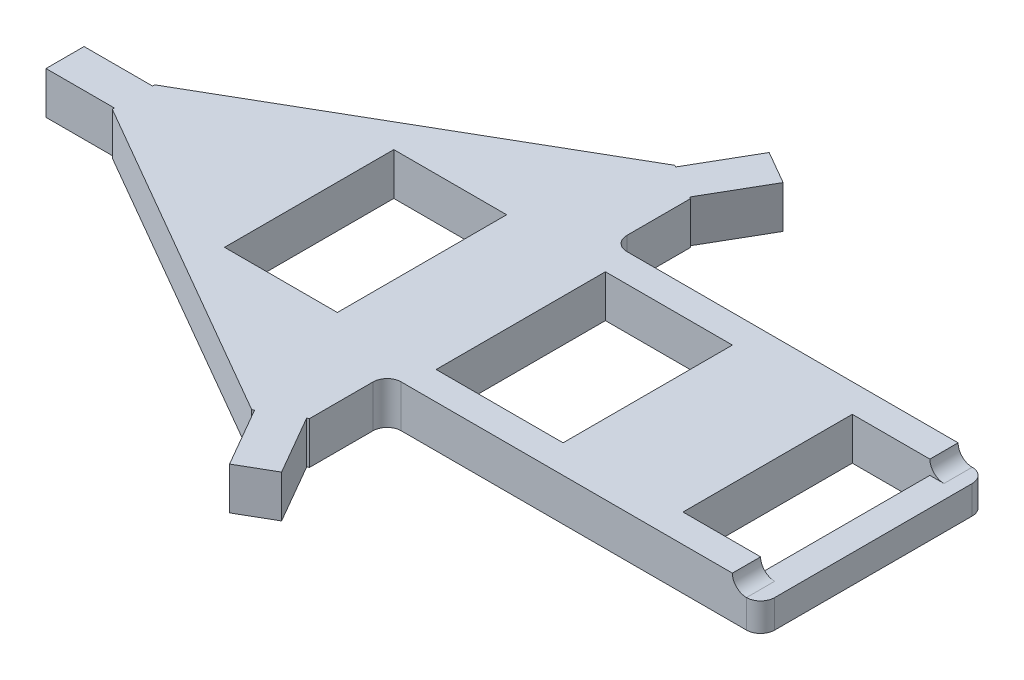
SolidWorks part; units mm, degrees
ref_plane "Front Plane" through (0, 0, 0) normal (0, 0, 1) x (1, 0, 0)
ref_plane "Top Plane" through (0, 0, 0) normal (0, 1, 0) x (1, 0, 0)
ref_plane "Right Plane" through (0, 0, 0) normal (1, 0, 0) x (0, 0, -1)
sketch "Sketch1" plane through (0, 0, 0) normal (0, 1, 0) x (1, 0, 0)
  line L0 (0, 0) -> (101.6, 0)
  line L1 (0, 0) -> (-50.8, 87.9882)
  line L2 (0, 0) -> (-50.8, -87.9882)
  line L3 (20, -12.3081) -> (83, -12.3081)
  line L4 (20, -12.3081) -> (20, 12.3081)
  line L5 (83, -12.3081) -> (83, 12.3081)
  line L6 (20, 12.3081) -> (83, 12.3081)
  line L7 (20, -12.3081) -> (83, 12.3081) construction
  line L8 (83, -12.3081) -> (20, 12.3081) construction
  line L9 (83, 0) -> (83, -58.5966) construction
  line L10 (20, 12.3081) -> (0, 12.3081)
  line L11 (20, 12.3081) -> (20, -12.3081)
  line L12 (20, -12.3081) -> (0, -12.3081)
  line L13 (0, 12.3081) -> (0, -12.3081)
  line L14 (51.5, 12.3081) -> (51.5, -12.3081) construction
  line L15 (83, -58.5966) -> (119.7868, -58.5966)
  line L16 (83, -58.5966) -> (83, 61.6733)
  line L17 (83, 61.6733) -> (119.7868, 61.6733)
  line L18 (119.7868, -58.5966) -> (119.7868, 61.6733)
  line L19 (83, -8.5) -> (20, -8.5)
  line L20 (83, -8.5) -> (83, 8.5)
  line L21 (83, 8.5) -> (20, 8.5)
  line L22 (20, -8.5) -> (20, 8.5)
  line L23 (83, -8.5) -> (20, 8.5) construction
  line L24 (83, 8.5) -> (20, -8.5) construction
  line L25 (20, 8.5) -> (40, 8.5)
  line L26 (20, 8.5) -> (20, 12.3081)
  line L27 (20, 12.3081) -> (40, 12.3081)
  line L28 (40, 8.5) -> (40, 12.3081)
  line L29 (63, 8.5) -> (63, 12.3081)
  line L30 (63, -8.5) -> (63, -12.3081)
  line L31 (40, -8.5) -> (40, -12.3081)
  circle A0 centre (0, 0) radius 101.6
  circle A1 centre (0, 0) radius 20
  point P7 (51.5, 0)
  point P19 (51.5, 0)
  dimension "D1" = 120
  dimension "D8" = 203.2
  dimension "D2" = 120
  dimension "D3" = 63
  dimension "D4" = 20
  dimension "D5" = 0
  dimension "D6" = 17
  dimension "D7" = 20
sketch "Sketch2" plane through (0, 0, 0) normal (0, 1, 0) x (1, 0, 0)
  circle A0 centre (0, 0) radius 88.9
  dimension "D1" = 177.8
extrude "Boss-Extrude1" add sketch "Sketch2" along normal blind 3.175
sketch "Sketch4" plane through (0, 3.175, 0) normal (0, 1, 0) x (1, 0, 0)
  line L0 (-88.9, 0) -> (88.9, 0) construction
  line L1 (52.07, 0) -> (52.07, 13.9847) construction
  line L2 (16.51, 15.5) -> (38.51, 15.5)
  line L3 (16.51, 15.5) -> (16.51, -15.5)
  line L4 (16.51, -15.5) -> (38.51, -15.5)
  line L5 (38.51, 15.5) -> (38.51, -15.5)
  line L6 (16.51, 15.5) -> (38.51, -15.5) construction
  line L7 (16.51, -15.5) -> (38.51, 15.5) construction
  line L8 (-16.51, -16.51) -> (16.51, -16.51)
  line L9 (-16.51, -16.51) -> (-16.51, 16.51)
  line L10 (-16.51, 16.51) -> (16.51, 16.51)
  line L11 (16.51, -16.51) -> (16.51, 16.51)
  line L12 (-16.51, -16.51) -> (16.51, 16.51) construction
  line L13 (-16.51, 16.51) -> (16.51, -16.51) construction
  line L14 (16.51, 15.5) -> (23.51, 15.5)
  line L15 (16.51, 15.5) -> (16.51, -15.5)
  line L16 (16.51, -15.5) -> (23.51, -15.5)
  line L17 (23.51, 15.5) -> (23.51, -15.5)
  line L18 (23.51, 8.5) -> (38.51, 8.5)
  line L19 (23.51, 8.5) -> (23.51, -8.5)
  line L20 (23.51, -8.5) -> (38.51, -8.5)
  line L21 (38.51, 8.5) -> (38.51, -8.5)
  line L22 (80.63, -8.5) -> (65.63, -8.5)
  line L23 (65.63, 8.5) -> (65.63, -8.5)
  line L24 (80.63, 8.5) -> (65.63, 8.5)
  line L25 (80.63, 8.5) -> (80.63, -8.5)
  line L26 (87.63, -15.5) -> (65.63, -15.5)
  line L27 (65.63, 15.5) -> (65.63, -15.5)
  line L28 (87.63, 15.5) -> (65.63, 15.5)
  line L29 (87.63, 15.5) -> (87.63, -15.5)
  line L30 (87.63, -15.5) -> (80.63, -15.5)
  line L31 (80.63, 15.5) -> (80.63, -15.5)
  line L32 (87.63, 15.5) -> (80.63, 15.5)
  line L33 (87.63, 15.5) -> (87.63, -15.5)
  line L34 (80.63, -31.75) -> (80.63, 31.75)
  line L35 (80.63, -31.75) -> (102.0422, -31.75)
  line L36 (80.63, 31.75) -> (102.0422, 31.75)
  line L37 (102.0422, -31.75) -> (102.0422, 31.75)
  circle A1 centre (0, 0) radius 88.9
  circle A2 centre (0, 0) radius 88.9
  point P5 (27.51, 0)
  dimension "D2" = 22
  dimension "D3" = 33.02
  dimension "D4" = 33.02
  dimension "D5" = 31
  dimension "D6" = 0
  dimension "D7" = 7
  dimension "D8" = 17
  dimension "D9" = 8.5
  dimension "D10" = 35.56
  dimension "D11" = 63.5
  dimension "D12" = 31.75
  dimension "D1" = 0
extrude "Cut-Extrude2" cut sketch "Sketch4" against normal through all contours L17 L2 L3 L4 | L25 L24 L23 L22 | L17 L20 L5 L18 | L34 L35 L37 L36 region at (20.01, 3.175, 0) region at (31.01, 3.175, 0) region at (73.13, 3.175, 0)
pattern_circular "CirPattern1" count 3 over 360 about axis through (0, 3.175, 0) along (0, 1, 0) of "Cut-Extrude2"
sketch "Sketch5" plane through (0, 3.175, 0) normal (0, 1, 0) x (1, 0, 0)
  line L1 (-16.51, -15.5) -> (16.51, -15.5)
  line L2 (-16.51, -15.5) -> (-16.51, 15.5)
  line L3 (-16.51, 15.5) -> (16.51, 15.5)
  line L4 (16.51, -15.5) -> (16.51, 15.5)
  line L5 (-16.51, -15.5) -> (16.51, 15.5) construction
  line L6 (-16.51, 15.5) -> (16.51, -15.5) construction
  line L7 (-5.49, -15.5) -> (16.51, -15.5)
  line L8 (-5.49, -15.5) -> (-5.49, 15.5)
  line L9 (-5.49, 15.5) -> (16.51, 15.5)
  line L10 (16.51, -15.5) -> (16.51, 15.5)
  line L11 (-5.49, -15.5) -> (16.51, 15.5) construction
  line L12 (-5.49, 15.5) -> (16.51, -15.5) construction
  point P0 (0, 0)
  point P7 (5.51, 0)
  dimension "D1" = 22
sketch "Sketch6" plane through (0, 3.175, 0) normal (0, 1, 0) x (1, 0, 0)
  line L0 (5.1684, 22.0481) -> (16.51, 15.5)
  line L1 (16.51, 15.5) -> (16.51, -15.5)
  line L2 (16.51, -15.5) -> (5.1684, -22.0481)
  line L3 (5.1684, -22.0481) -> (-21.6784, -6.5481)
  line L4 (-21.6784, -6.5481) -> (-21.6784, 6.5481)
  line L5 (-21.6784, 6.5481) -> (5.1684, 22.0481)
  line L21 (-32.9538, -74.0776) -> (-12.8187, -85.7026)
  line L24 (80.63, -31.75) -> (80.63, -8.5)
  line L25 (80.63, -8.5) -> (65.63, -8.5)
  line L26 (65.63, -8.5) -> (65.63, 8.5)
  line L27 (65.63, 8.5) -> (80.63, 8.5)
  line L28 (80.63, 8.5) -> (80.63, 31.75)
  line L31 (-12.8187, 85.7026) -> (-32.9538, 74.0776)
  line L32 (-32.9538, 74.0776) -> (-25.4538, 61.0872)
  line L33 (-25.4538, 61.0872) -> (-40.1762, 52.5872)
  line L34 (-40.1762, 52.5872) -> (-47.6762, 65.5776)
  line L35 (-47.6762, 65.5776) -> (-67.8113, 53.9526)
  line L38 (-67.8113, -53.9526) -> (-47.6762, -65.5776)
  line L39 (-47.6762, -65.5776) -> (-40.1762, -52.5872)
  line L40 (-40.1762, -52.5872) -> (-25.4538, -61.0872)
  line L41 (-25.4538, -61.0872) -> (-32.9538, -74.0776)
  line L42 (-32.9538, -74.0776) -> (-12.8187, -85.7026)
  line L45 (80.63, -31.75) -> (80.63, -8.5)
  line L46 (80.63, -8.5) -> (65.63, -8.5)
  line L47 (65.63, -8.5) -> (65.63, 8.5)
  line L48 (65.63, 8.5) -> (80.63, 8.5)
  line L49 (80.63, 8.5) -> (80.63, 31.75)
  line L52 (-12.8187, 85.7026) -> (-32.9538, 74.0776)
  line L53 (-32.9538, 74.0776) -> (-25.4538, 61.0872)
  line L54 (-25.4538, 61.0872) -> (-40.1762, 52.5872)
  line L55 (-40.1762, 52.5872) -> (-47.6762, 65.5776)
  line L56 (-47.6762, 65.5776) -> (-67.8113, 53.9526)
  line L59 (-67.8113, -53.9526) -> (-47.6762, -65.5776)
  line L60 (-47.6762, -65.5776) -> (-40.1762, -52.5872)
  line L61 (-40.1762, -52.5872) -> (-25.4538, -61.0872)
  line L62 (-25.4538, -61.0872) -> (-32.9538, -74.0776)
  line L63 (-12.8187, -85.7026) -> (-14.0222, -87.7872)
  line L64 (-12.8187, -85.7026) -> (-14.0222, -87.7872)
  line L65 (83.037, -31.75) -> (80.63, -31.75)
  line L66 (83.037, -31.75) -> (80.63, -31.75)
  line L67 (80.63, 31.75) -> (83.037, 31.75)
  line L68 (80.63, 31.75) -> (83.037, 31.75)
  line L69 (-14.0222, 87.7872) -> (-12.8187, 85.7026)
  line L70 (-14.0222, 87.7872) -> (-12.8187, 85.7026)
  line L71 (-67.8113, 53.9526) -> (-69.0148, 56.0372)
  line L72 (-67.8113, 53.9526) -> (-69.0148, 56.0372)
  line L73 (-69.0148, -56.0372) -> (-67.8113, -53.9526)
  line L74 (-69.0148, -56.0372) -> (-67.8113, -53.9526)
  arc A3 (-14.0222, -87.7872) -> (83.037, -31.75) centre (0, 0) ccw
  arc A5 (-14.0222, -87.7872) -> (83.037, -31.75) centre (0, 0) ccw
  arc A10 (83.037, 31.75) -> (-14.0222, 87.7872) centre (0, 0) ccw
  arc A12 (83.037, 31.75) -> (-14.0222, 87.7872) centre (0, 0) ccw
  arc A13 (-69.0148, 56.0372) -> (-69.0148, -56.0372) centre (0, 0) ccw
  arc A14 (-69.0148, 56.0372) -> (-69.0148, -56.0372) centre (0, 0) ccw
  line M38 (16.51, -15.5) -> (16.51, 15.5)
  line M46 (-21.6784, -6.5481) -> (5.1684, -22.0481)
  line M78 (5.1684, 22.0481) -> (-21.6784, 6.5481)
  dimension "D1" = 0
extrude "Cut-Extrude3" cut sketch "Sketch6" against normal through all contours L4 L2 L0 M46 M38 M78 region at (0, 3.175, 0)
sketch "Sketch8" plane through (0, 3.175, 0) normal (0, 1, 0) x (1, 0, 0)
  circle A0 centre (0, 0) radius 86.656
extrude "Cut-Extrude-Thin1" cut sketch "Sketch8" against normal through all thin thin type one direction wall 7.62
sketch "Sketch9" plane through (0, 3.175, 0) normal (0, 1, 0) x (1, 0, 0)
  line L0 (0, 0) -> (98.7445, 0) construction
  line L2 (8.8329, -24.13) -> (65.5497, -24.13)
  line L3 (8.8329, -24.13) -> (8.8329, 24.13)
  line L4 (8.8329, 24.13) -> (65.5497, 24.13)
  line L5 (65.5497, -24.13) -> (65.5497, 24.13)
  line L6 (8.8329, -24.13) -> (65.5497, 24.13) construction
  line L7 (8.8329, 24.13) -> (65.5497, -24.13) construction
  circle A0 centre (0, 0) radius 69.85
  circle A1 centre (65.5497, 24.13) radius 3.175
  circle A2 centre (65.5497, -24.13) radius 3.175
  point P3 (37.1913, 0)
  dimension "D1" = 48.26
  dimension "D2" = 139.7
extrude "Cut-Extrude4" cut sketch "Sketch9" against normal through all contours A1 | A2
pattern_circular "CirPattern2" count 3 over 360 about axis through (0, 3.175, 0) along (0, 1, 0) of "Cut-Extrude4"
sketch "Sketch10" plane through (0, 3.175, 0) normal (0, 1, 0) x (1, 0, 0)
  line L0 (43.328, 75.0463) -> (0, 0)
  line L1 (49.8459, 15.2156) -> (75.2459, 59.2097)
  line L2 (49.8459, 15.2156) -> (-11.7459, 50.7756)
  line L3 (75.2459, 59.2097) -> (13.6541, 94.7697)
  line L4 (-11.7459, 50.7756) -> (13.6541, 94.7697)
  line L5 (49.8459, 15.2156) -> (13.6541, 94.7697) construction
  line L6 (75.2459, 59.2097) -> (-11.7459, 50.7756) construction
  circle A0 centre (43.328, 75.0463) radius 38.1
  arc A1 (80.63, 31.75) -> (-12.8187, 85.7026) centre (0, 0) ccw construction
  point P8 (31.75, 54.9926)
  dimension "D1" = 71.12
  dimension "D2" = 35.56
  dimension "D3" = 50.8
  dimension "D4" = 63.5
sketch "Sketch11" plane through (0, 3.175, 0) normal (0, 1, 0) x (1, 0, 0)
  line L0 (-21.6784, -6.5481) -> (-21.6784, 6.5481) construction
  line L1 (0, 0) -> (-111.2988, 0)
  line L2 (-23.9644, -36.83) -> (-74.7644, -36.83)
  line L3 (-23.9644, -36.83) -> (-23.9644, 36.83)
  line L4 (-23.9644, 36.83) -> (-74.7644, 36.83)
  line L5 (-74.7644, -36.83) -> (-74.7644, 36.83)
  line L6 (-23.9644, -36.83) -> (-74.7644, 36.83) construction
  line L7 (-23.9644, 36.83) -> (-74.7644, -36.83) construction
  line L12 (-23.9644, -6.35) -> (-23.9644, 6.35)
  line L16 (-23.9644, 6.35) -> (-23.9644, -6.35)
  line L19 (-76.3519, 36.83) -> (-73.1769, 36.83)
  line L20 (-76.3519, 36.83) -> (-76.3519, 24.13)
  line L21 (-76.3519, 24.13) -> (-73.1769, 24.13)
  line L22 (-73.1769, 36.83) -> (-73.1769, 24.13)
  line L23 (-74.7644, 38.4175) -> (-62.0644, 38.4175)
  line L24 (-74.7644, 38.4175) -> (-74.7644, 35.2425)
  line L25 (-74.7644, 35.2425) -> (-62.0644, 35.2425)
  line L26 (-62.0644, 38.4175) -> (-62.0644, 35.2425)
  line L28 (-23.9644, 0) -> (-23.9644, 3.81)
  circle A0 centre (-74.7644, 36.83) radius 1.5875
  circle A1 centre (-62.0644, 36.83) radius 1.5875
  circle A2 centre (-74.7644, 24.13) radius 1.5875
  circle A4 centre (-74.7644, 36.83) radius 3.175
  point P3 (-49.3644, 0)
  point P8 (-23.2024, 0)
  dimension "D7" = 3.175
  dimension "D8" = 3.175
  dimension "D9" = 3.175
  dimension "D6" = 6.35
  dimension "D1" = 50.8
  dimension "D2" = 73.66
  dimension "D3" = 2.286
  dimension "D4" = 0
  dimension "D5" = 0
  dimension "D10" = 12.7
  dimension "D11" = 12.7
extrude "Cut-Extrude6" cut sketch "Sketch11" against normal through all contours A0 | A1 | A2
mirror "Mirror1" about plane through (0, 0, 0) normal (0, 0, 1) of "Cut-Extrude6"
pattern_circular "CirPattern3" count 2 every 120 about axis through (0, 3.175, 0) along (0, 1, 0) of "Mirror1", "Cut-Extrude6"
sketch "Sketch12" plane through (0, 3.175, 0) normal (0, 1, 0) x (1, 0, 0)
  line L2 (0, 0) -> (-49.928, 0) construction
  line L3 (-21.6784, -6.5481) -> (-21.6784, 6.5481) construction
  line L4 (-25.4884, -6.35) -> (-21.6784, -6.35)
  line L5 (-25.4884, -6.35) -> (-25.4884, 6.35)
  line L6 (-25.4884, 6.35) -> (-21.6784, 6.35)
  line L7 (-21.6784, -6.35) -> (-21.6784, 6.35)
  line L8 (-25.4884, -6.35) -> (-21.6784, 6.35) construction
  line L9 (-25.4884, 6.35) -> (-21.6784, -6.35) construction
  line L12 (-25.4884, 6.35) -> (-25.4884, -6.35)
  circle A0 centre (-25.4884, 3.81) radius 1.5875
  circle A1 centre (-25.4884, -3.81) radius 1.5875
  circle A2 centre (-33.1084, 0) radius 1.5875
  point P0 (-23.5834, 0)
  dimension "D3" = 3.175
  dimension "D4" = 3.175
  dimension "D7" = 3.175
  dimension "D1" = 3.81
  dimension "D2" = 12.7
  dimension "D5" = 7.62
  dimension "D6" = 3.81
  dimension "D8" = 7.62
extrude "Cut-Extrude7" cut sketch "Sketch12" against normal through all contours A2 | L12 A0 | L12 A0 | L12 A1 | L12 A1 region at (-26.1621, 3.175, 3.81) region at (-24.8146, 3.175, 3.81) region at (-26.1621, 3.175, -3.81) region at (-24.8146, 3.175, -3.81) region at (-33.1084, 3.175, 0)
pattern_circular "CirPattern4" count 2 every 120 about axis through (0, 3.175, 0) along (0, 1, 0) of "Cut-Extrude7"
extrude "Cut-Extrude8" cut sketch "Sketch10" against normal blind 150 contours L3 L4 L2 L1
fillet "Fillet1" radius 22.86 2 edges at (49.8459, 1.5875, -15.2156) (-11.7459, 1.5875, -50.7756)
sketch "Sketch13" plane through (0, 3.175, 0) normal (0, 1, 0) x (1, 0, 0)
  line L0 (-21.6784, 6.5481) -> (5.1684, 22.0481)
  line L1 (5.1684, 22.0481) -> (16.51, 15.5)
  line L2 (16.51, 15.5) -> (16.51, -15.5)
  line L3 (16.51, -15.5) -> (5.1684, -22.0481)
  line L4 (5.1684, -22.0481) -> (-21.6784, -6.5481)
  line L5 (-21.6784, -6.5481) -> (-21.6784, 6.5481)
  line L18 (70.3077, 50.6565) -> (61.2759, 35.0129)
  line L19 (30.0485, 26.6456) -> (8.0515, 39.3456)
  line L20 (-0.3159, 70.5729) -> (8.716, 86.2165)
  line L21 (-12.8187, 85.7026) -> (-32.9538, 74.0776)
  line L22 (-32.9538, 74.0776) -> (-25.4538, 61.0872)
  line L23 (-25.4538, 61.0872) -> (-40.1762, 52.5872)
  line L24 (-40.1762, 52.5872) -> (-47.6762, 65.5776)
  line L25 (-47.6762, 65.5776) -> (-67.8113, 53.9526)
  line L26 (-67.8113, -53.9526) -> (-47.6762, -65.5776)
  line L27 (-47.6762, -65.5776) -> (-40.1762, -52.5872)
  line L28 (-40.1762, -52.5872) -> (-25.4538, -61.0872)
  line L29 (-25.4538, -61.0872) -> (-32.9538, -74.0776)
  line L30 (-32.9538, -74.0776) -> (-12.8187, -85.7026)
  line L31 (80.63, -31.75) -> (80.63, -8.5)
  line L32 (80.63, -8.5) -> (65.63, -8.5)
  line L33 (65.63, -8.5) -> (65.63, 8.5)
  line L34 (65.63, 8.5) -> (80.63, 8.5)
  line L35 (80.63, 8.5) -> (80.63, 31.75)
  line L36 (70.3077, 50.6565) -> (61.2759, 35.0129)
  line L37 (30.0485, 26.6456) -> (8.0515, 39.3456)
  line L38 (-0.3159, 70.5729) -> (8.716, 86.2165)
  line L39 (-12.8187, 85.7026) -> (-32.9538, 74.0776)
  line L40 (-32.9538, 74.0776) -> (-25.4538, 61.0872)
  line L41 (-25.4538, 61.0872) -> (-40.1762, 52.5872)
  line L42 (-40.1762, 52.5872) -> (-47.6762, 65.5776)
  line L43 (-47.6762, 65.5776) -> (-67.8113, 53.9526)
  line L44 (-67.8113, -53.9526) -> (-47.6762, -65.5776)
  line L45 (-47.6762, -65.5776) -> (-40.1762, -52.5872)
  line L46 (-40.1762, -52.5872) -> (-25.4538, -61.0872)
  line L47 (-25.4538, -61.0872) -> (-32.9538, -74.0776)
  line L48 (-32.9538, -74.0776) -> (-12.8187, -85.7026)
  line L49 (80.63, -31.75) -> (80.63, -8.5)
  line L50 (80.63, -8.5) -> (65.63, -8.5)
  line L51 (65.63, -8.5) -> (65.63, 8.5)
  line L52 (65.63, 8.5) -> (80.63, 8.5)
  line L53 (80.63, 8.5) -> (80.63, 31.75)
  arc A6 (30.0485, 26.6456) -> (61.2759, 35.0129) centre (41.4785, 46.4429) ccw
  arc A7 (-0.3159, 70.5729) -> (8.0515, 39.3456) centre (19.4815, 59.1429) ccw
  arc A8 (8.716, 86.2165) -> (-12.8187, 85.7026) centre (0, 0) ccw
  arc A9 (-67.8113, 53.9526) -> (-67.8113, -53.9526) centre (0, 0) ccw
  arc A10 (-12.8187, -85.7026) -> (80.63, -31.75) centre (0, 0) ccw
  arc A11 (80.63, 31.75) -> (70.3077, 50.6565) centre (0, 0) ccw
  arc A12 (30.0485, 26.6456) -> (61.2759, 35.0129) centre (41.4785, 46.4429) ccw
  arc A13 (-0.3159, 70.5729) -> (8.0515, 39.3456) centre (19.4815, 59.1429) ccw
  arc A14 (8.716, 86.2165) -> (-12.8187, 85.7026) centre (0, 0) ccw
  arc A15 (-67.8113, 53.9526) -> (-67.8113, -53.9526) centre (0, 0) ccw
  arc A16 (-12.8187, -85.7026) -> (80.63, -31.75) centre (0, 0) ccw
  arc A17 (80.63, 31.75) -> (70.3077, 50.6565) centre (0, 0) ccw
  dimension "D1" = 0
sketch "Sketch14" plane through (0, 3.175, 0) normal (0, 1, 0) x (1, 0, 0)
  line L0 (16.51, -15.5) -> (5.1684, -22.0481) construction
  line L1 (5.1684, 22.0481) -> (16.51, 15.5) construction
  line L2 (16.51, 15.5) -> (16.51, -15.5) construction
  line L3 (5.1684, -22.0481) -> (-21.6784, -6.5481) construction
  line L4 (-21.6784, -6.5481) -> (-21.6784, 6.5481) construction
  line L5 (-21.6784, 6.5481) -> (5.1684, 22.0481) construction
  line L6 (16.51, -15.5) -> (5.1684, -22.0481)
  line L7 (5.1684, 22.0481) -> (16.51, 15.5)
  line L8 (16.51, 15.5) -> (16.51, -15.5)
  line L9 (5.1684, -22.0481) -> (-21.6784, -6.5481)
  line L10 (-21.6784, -6.5481) -> (-21.6784, 6.5481)
  line L11 (-21.6784, 6.5481) -> (5.1684, 22.0481)
sketch "Sketch15" plane through (0, 3.175, 0) normal (0, 1, 0) x (1, 0, 0)
  line L6 (5.1684, -22.0481) -> (16.51, -15.5)
  line L7 (-21.6784, -6.5481) -> (5.1684, -22.0481)
  line L8 (-21.6784, 6.5481) -> (-21.6784, -6.5481)
  line L9 (5.1684, 22.0481) -> (-21.6784, 6.5481)
  line L10 (16.51, 15.5) -> (5.1684, 22.0481)
  line L11 (16.51, -15.5) -> (16.51, 15.5)
  line L12 (5.1684, -22.0481) -> (16.51, -15.5)
  line L13 (-21.6784, -6.5481) -> (5.1684, -22.0481)
  line L14 (-21.6784, 6.5481) -> (-21.6784, -6.5481)
  line L15 (5.1684, 22.0481) -> (-21.6784, 6.5481)
  line L16 (16.51, 15.5) -> (5.1684, 22.0481)
  line L17 (16.51, -15.5) -> (16.51, 15.5)
  circle A0 centre (0, 0) radius 86.656
  dimension "D1" = 0
extrude "Boss-Extrude2" add sketch "Sketch15" along normal blind 3 separate body contours L12 L17 L16 L15 L14 L13 region at (0, 3.175, 0)
sketch "Sketch16" plane through (0, 3.175, 0) normal (0, 1, 0) x (1, 0, 0)
  line L6 (5.1684, -22.0481) -> (16.51, -15.5)
  line L7 (16.51, -15.5) -> (16.51, 15.5)
  line L8 (16.51, 15.5) -> (5.1684, 22.0481)
  line L9 (5.1684, 22.0481) -> (-21.6784, 6.5481)
  line L10 (-21.6784, 6.5481) -> (-21.6784, -6.5481)
  line L11 (-21.6784, -6.5481) -> (5.1684, -22.0481)
  line L12 (5.1684, -22.0481) -> (16.51, -15.5)
  line L13 (16.51, -15.5) -> (16.51, 15.5)
  line L14 (16.51, 15.5) -> (5.1684, 22.0481)
  line L15 (5.1684, 22.0481) -> (-21.6784, 6.5481)
  line L16 (-21.6784, 6.5481) -> (-21.6784, -6.5481)
  line L17 (-21.6784, -6.5481) -> (5.1684, -22.0481)
  circle A0 centre (0, 0) radius 86.656
  dimension "D1" = 0
extrude "Cut-Extrude10" cut sketch "Sketch16" against normal through all contours A0 L17 L16 L15 L14 L13 L12 region at (-84.205, 3.175, 0)
sketch "Sketch17" plane through (-21.6784, 0, 0) normal (-1, 0, 0) x (0, 0, 1)
  line L0 (-6.5481, 3.175) -> (6.5481, 3.175) construction
  line L1 (-6.5481, 6.175) -> (6.5481, 6.175)
  line L2 (-6.5481, 6.175) -> (-6.5481, 3.175)
  line L3 (-6.5481, 3.175) -> (6.5481, 3.175)
  line L4 (6.5481, 6.175) -> (6.5481, 3.175)
  line L5 (0, 6.175) -> (0, 3.175) construction
  line L6 (6.5481, 6.175) -> (6.5481, 3.175) construction
  line L7 (-1.5, 3.175) -> (1.5, 3.175)
  line L8 (-1.5, 3.175) -> (-1.5, 6.175)
  line L9 (-1.5, 6.175) -> (1.5, 6.175)
  line L10 (1.5, 3.175) -> (1.5, 6.175)
  line L11 (-1.5, 3.175) -> (1.5, 6.175) construction
  line L12 (-1.5, 6.175) -> (1.5, 3.175) construction
  point P9 (0, 4.675)
  dimension "D1" = 3
  dimension "D2" = 0
extrude "Boss-Extrude3" add sketch "Sketch17" along normal blind 2 contours L3 L10 L1 L8 region at (-21.6784, 4.675, 0)
sketch "Sketch18" plane through (0, 6.175, 0) normal (0, 1, 0) x (1, 0, 0)
  circle A0 centre (0, 0) radius 22.6458
  circle A1 centre (0, 0) radius 21.6784
extrude "Boss-Extrude4" add sketch "Sketch18" against normal blind 3 contours A1
sketch "Sketch19" plane through (0, 6.175, 0) normal (0, 1, 0) x (1, 0, 0)
  line L0 (13.1382, 19.7561) -> (10.5402, 21.2561)
  line L1 (10.5402, 21.2561) -> (9.5402, 19.524)
  line L2 (12.1382, 18.024) -> (13.1382, 19.7561)
  line L3 (10.5402, -21.2561) -> (13.1382, -19.7561)
  line L4 (13.1382, -19.7561) -> (12.1382, -18.024)
  line L5 (9.5402, -19.524) -> (10.5402, -21.2561)
  line L6 (-21.6784, 1.5) -> (9.5402, 19.524)
  line L7 (12.1382, 18.024) -> (12.1382, -18.024)
  line L8 (9.5402, -19.524) -> (-21.6784, -1.5)
  line L9 (-23.6784, 0) -> (12.1382, 0) construction
  line L10 (11.8392, 20.5061) -> (-6.0691, -10.512) construction
  line L11 (11.8392, -20.5061) -> (-6.0691, 10.512) construction
  line L12 (9.5402, -19.524) -> (-21.6784, -1.5)
  line L13 (-21.6784, -6.5481) -> (-20.4217, -7.2736)
  line L14 (3.9117, -21.3225) -> (5.1684, -22.0481)
  line L15 (5.1684, -22.0481) -> (16.51, -15.5)
  line L16 (16.51, -15.5) -> (16.51, -14.0489)
  line L17 (16.51, 14.0489) -> (16.51, 15.5)
  line L18 (16.51, 15.5) -> (5.1684, 22.0481)
  line L19 (5.1684, 22.0481) -> (3.9117, 21.3225)
  line L20 (-20.4217, 7.2736) -> (-21.6784, 6.5481)
  line L21 (-21.6784, 6.5481) -> (-21.6784, 1.5)
  line L22 (-21.6784, 1.5) -> (-23.6784, 1.5)
  line L23 (-23.6784, 1.5) -> (-23.6784, -1.5)
  line L24 (-23.6784, -1.5) -> (-21.6784, -1.5)
  line L25 (-21.6784, -1.5) -> (-21.6784, -6.5481)
  line L26 (-21.6784, -6.5481) -> (-20.4217, -7.2736)
  line L27 (3.9117, -21.3225) -> (5.1684, -22.0481)
  line L28 (5.1684, -22.0481) -> (16.51, -15.5)
  line L29 (16.51, -15.5) -> (16.51, -14.0489)
  line L30 (16.51, 14.0489) -> (16.51, 15.5)
  line L31 (16.51, 15.5) -> (5.1684, 22.0481)
  line L32 (5.1684, 22.0481) -> (3.9117, 21.3225)
  line L33 (-20.4217, 7.2736) -> (-21.6784, 6.5481)
  line L34 (-21.6784, 6.5481) -> (-21.6784, 1.5)
  line L35 (-21.6784, 1.5) -> (-23.6784, 1.5)
  line L36 (-23.6784, 1.5) -> (-23.6784, -1.5)
  line L37 (-23.6784, -1.5) -> (-21.6784, -1.5)
  line L38 (-21.6784, -1.5) -> (-21.6784, -6.5481)
  line L39 (12.1382, 18.024) -> (9.1382, 18.024)
  line L40 (12.1382, 18.024) -> (12.1382, -18.024)
  line L41 (12.1382, -18.024) -> (9.1382, -18.024)
  line L42 (9.1382, 18.024) -> (9.1382, -18.024)
  line L43 (9.5402, -19.524) -> (11.0402, -16.926)
  line L44 (11.0402, -16.926) -> (-20.1784, 1.0981)
  line L45 (-21.6784, -1.5) -> (-20.1784, 1.0981)
  line L46 (-21.6784, 1.5) -> (9.5402, 19.524)
  line L47 (-21.6784, 1.5) -> (-20.1784, -1.0981)
  line L48 (-20.1784, -1.0981) -> (11.0402, 16.926)
  line L49 (9.5402, 19.524) -> (11.0402, 16.926)
  line L50 (-4.5691, -7.9139) -> (-4.5691, 7.9139)
  line L51 (-4.5691, 7.9139) -> (9.1382, 0)
  line L52 (9.1382, 0) -> (-4.5691, -7.9139)
  line L53 (-4.5691, 9.646) -> (10.6382, 0.866)
  line L54 (-6.0691, -8.78) -> (-3.0691, -8.78)
  line L55 (-6.0691, -8.78) -> (-6.0691, 8.78)
  line L56 (-6.0691, 8.78) -> (-3.0691, 8.78)
  line L57 (-3.0691, -8.78) -> (-3.0691, 8.78)
  line L58 (-6.0691, -8.78) -> (-3.0691, 8.78) construction
  line L59 (-6.0691, 8.78) -> (-3.0691, -8.78) construction
  line L60 (-4.5691, 9.646) -> (-6.0691, 7.0479)
  line L61 (-6.0691, 7.0479) -> (9.1382, -1.7321)
  line L62 (10.6382, 0.866) -> (9.1382, -1.7321)
  line L63 (10.6382, -0.866) -> (-4.5691, -9.646)
  line L64 (10.6382, -0.866) -> (9.1382, 1.7321)
  line L65 (9.1382, 1.7321) -> (-6.0691, -7.0479)
  line L66 (-4.5691, -9.646) -> (-6.0691, -7.0479)
  arc A3 (-20.4217, -7.2736) -> (3.9117, -21.3225) centre (0, 0) ccw
  arc A4 (16.51, -14.0489) -> (16.51, 14.0489) centre (0, 0) ccw
  arc A5 (3.9117, 21.3225) -> (-20.4217, 7.2736) centre (0, 0) ccw
  arc A6 (-20.4217, -7.2736) -> (3.9117, -21.3225) centre (0, 0) ccw
  arc A7 (16.51, -14.0489) -> (16.51, 14.0489) centre (0, 0) ccw
  arc A8 (3.9117, 21.3225) -> (-20.4217, 7.2736) centre (0, 0) ccw
  point P27 (0, 0)
  point P47 (0, 0)
  point P48 (-4.5691, 0)
  point P63 (0, 0)
  dimension "D3" = 3
  dimension "D5" = 15.8279
  dimension "D6" = 3
  dimension "D1" = 0
  dimension "D2" = 3
  dimension "D4" = 3
  dimension "D7" = 3
sketch "Sketch20" plane through (0, 6.175, 0) normal (0, 1, 0) x (1, 0, 0)
  line L0 (12.1382, 18.024) -> (13.1382, 19.7561) construction
  line L1 (13.1382, 19.7561) -> (10.5402, 21.2561) construction
  line L2 (10.5402, 21.2561) -> (9.5402, 19.524) construction
  line L3 (-21.6784, 1.5) -> (9.5402, 19.524) construction
  line L4 (12.1382, 18.024) -> (12.1382, -18.024) construction
  line L6 (9.1382, 18.024) -> (9.1382, -18.024) construction
  line L8 (12.1382, 18.024) -> (12.1382, -18.024) construction
  line L9 (-21.6784, -1.5) -> (-21.6784, -6.5481) construction
  line L10 (-21.6784, -6.5481) -> (-20.4217, -7.2736) construction
  line L11 (3.9117, -21.3225) -> (5.1684, -22.0481) construction
  line L12 (5.1684, -22.0481) -> (16.51, -15.5) construction
  line L13 (16.51, -15.5) -> (16.51, -14.0489) construction
  line L14 (16.51, 14.0489) -> (16.51, 15.5) construction
  line L15 (16.51, 15.5) -> (5.1684, 22.0481) construction
  line L16 (5.1684, 22.0481) -> (3.9117, 21.3225) construction
  line L17 (-20.4217, 7.2736) -> (-21.6784, 6.5481) construction
  line L18 (-21.6784, 6.5481) -> (-21.6784, 1.5) construction
  line L19 (-21.6784, 1.5) -> (-23.6784, 1.5) construction
  line L20 (-23.6784, 1.5) -> (-23.6784, -1.5) construction
  line L21 (-23.6784, -1.5) -> (-21.6784, -1.5) construction
  line L22 (13.1382, -19.7561) -> (12.1382, -18.024) construction
  line L23 (10.5402, -21.2561) -> (13.1382, -19.7561) construction
  line L24 (9.5402, -19.524) -> (10.5402, -21.2561) construction
  line L25 (9.5402, -19.524) -> (-21.6784, -1.5) construction
  line L29 (-21.6784, 1.5) -> (9.5402, 19.524) construction
  line L31 (-20.1784, -1.0981) -> (11.0402, 16.926) construction
  line L33 (9.5402, -19.524) -> (-21.6784, -1.5) construction
  line L35 (11.0402, -16.926) -> (-20.1784, 1.0981) construction
  line L37 (10.6382, -0.866) -> (-4.5691, -9.646) construction
  line L39 (9.1382, 1.7321) -> (-6.0691, -7.0479) construction
  line L42 (-3.0691, -8.78) -> (-3.0691, 8.78) construction
  line L44 (-6.0691, -8.78) -> (-6.0691, 8.78) construction
  line L47 (-6.0691, 7.0479) -> (9.1382, -1.7321) construction
  line L49 (12.1382, 18.024) -> (13.1382, 19.7561)
  line L50 (13.1382, 19.7561) -> (10.5402, 21.2561)
  line L51 (10.5402, 21.2561) -> (9.5402, 19.524)
  line L52 (-21.6784, 1.5) -> (9.5402, 19.524)
  line L53 (12.1382, 18.024) -> (12.1382, -18.024)
  line L55 (9.1382, 15.8279) -> (9.1382, 1.7321)
  line L57 (12.1382, 18.024) -> (12.1382, -18.024)
  line L58 (-21.6784, -1.5) -> (-21.6784, -6.5481)
  line L59 (-21.6784, -6.5481) -> (-20.4217, -7.2736)
  line L60 (3.9117, -21.3225) -> (5.1684, -22.0481)
  line L61 (5.1684, -22.0481) -> (16.51, -15.5)
  line L62 (16.51, -15.5) -> (16.51, -14.0489)
  line L63 (16.51, 14.0489) -> (16.51, 15.5)
  line L64 (16.51, 15.5) -> (12.1382, 18.024)
  line L65 (5.1684, 22.0481) -> (3.9117, 21.3225)
  line L66 (-20.4217, 7.2736) -> (-21.6784, 6.5481)
  line L67 (-21.6784, 6.5481) -> (-21.6784, 1.5)
  line L68 (-21.6784, 1.5) -> (-23.6784, 1.5)
  line L69 (-23.6784, 1.5) -> (-23.6784, -1.5)
  line L70 (-23.6784, -1.5) -> (-21.6784, -1.5)
  line L71 (13.1382, -19.7561) -> (12.1382, -18.024)
  line L72 (10.5402, -21.2561) -> (13.1382, -19.7561)
  line L73 (9.5402, -19.524) -> (10.5402, -21.2561)
  line L74 (9.5402, -19.524) -> (-21.6784, -1.5)
  line L78 (-21.6784, 1.5) -> (9.5402, 19.524)
  line L80 (-18.2765, 0) -> (-6.0691, 7.0479)
  line L81 (9.5402, 19.524) -> (5.1684, 22.0481)
  line L82 (9.5402, -19.524) -> (-21.6784, -1.5)
  line L83 (-6.0691, -7.0479) -> (-18.2765, 0)
  line L84 (9.1382, -15.8279) -> (-3.0691, -8.78)
  line L86 (9.1382, -1.7321) -> (-3.0691, -8.78)
  line L88 (6.1382, 0) -> (-3.0691, -5.3159)
  line L91 (-3.0691, -5.3159) -> (-3.0691, 5.3159)
  line L93 (-6.0691, -7.0479) -> (-6.0691, 7.0479)
  line L96 (-3.0691, 5.3159) -> (6.1382, 0)
  line L98 (9.1382, -1.7321) -> (9.1382, -15.8279)
  line L99 (-3.0691, 8.78) -> (9.1382, 15.8279)
  line L100 (-3.0691, 8.78) -> (9.1382, 1.7321)
  arc A0 (-20.4217, -7.2736) -> (3.9117, -21.3225) centre (0, 0) ccw construction
  arc A1 (16.51, -14.0489) -> (16.51, 14.0489) centre (0, 0) ccw construction
  arc A2 (3.9117, 21.3225) -> (-20.4217, 7.2736) centre (0, 0) ccw construction
  arc A3 (-20.4217, -7.2736) -> (3.9117, -21.3225) centre (0, 0) ccw
  arc A4 (16.51, -14.0489) -> (16.51, 14.0489) centre (0, 0) ccw
  arc A5 (3.9117, 21.3225) -> (-20.4217, 7.2736) centre (0, 0) ccw
  line M8 (16.51, 15.5) -> (5.1684, 22.0481)
  line M13 (-21.6784, 1.5) -> (-23.6784, 1.5)
  line M14 (-23.6784, 1.5) -> (-23.6784, -1.5)
  line M15 (-23.6784, -1.5) -> (-21.6784, -1.5)
extrude "Boss-Extrude5" add sketch "Sketch20" along normal blind 3 contours L74 L61 L53 L52 L100 L99 L55 L93 L83 L80 L91 L96 L88 L86 L98 L84 M8 M13 M14 M15 | L61 L73 L72 L71 | L50 L51 L49 M8 region at (11.3392, 6.175, -19.6401) region at (11.6084, 6.175, 0) region at (11.3392, 6.175, 19.6401)
sketch "Sketch21" plane through (-21.6784, 0, 0) normal (-1, 0, 0) x (0, 0, 1)
  line L1 (-66.1442, 0.175) -> (22.0481, 0.175)
  line L2 (-66.1442, 0.175) -> (-66.1442, 6.175)
  line L3 (-66.1442, 6.175) -> (22.0481, 6.175)
  line L4 (22.0481, 0.175) -> (22.0481, 6.175)
  line L5 (-66.1442, 0.175) -> (22.0481, 6.175) construction
  line L6 (-66.1442, 6.175) -> (22.0481, 0.175) construction
  point P0 (-22.0481, 3.175)
extrude "Cut-Extrude11" cut sketch "Sketch21" against normal through all both and the other way through all
sketch "Sketch23" plane through (0, 9.175, 0) normal (0, 1, 0) x (1, 0, 0)
  line L0 (13.1382, 19.7561) -> (10.5402, 21.2561)
  line L1 (-23.6784, 1.5) -> (-26.6784, 1.5)
  line L2 (-23.6784, 1.5) -> (-23.6784, -1.5)
  line L3 (-23.6784, -1.5) -> (-26.6784, -1.5)
  line L4 (-26.6784, 1.5) -> (-26.6784, -1.5)
  line L5 (13.1382, 19.7561) -> (14.6382, 22.3542)
  line L6 (14.6382, 22.3542) -> (12.0402, 23.8542)
  line L7 (10.5402, 21.2561) -> (12.0402, 23.8542)
  line L8 (10.5402, -21.2561) -> (13.1382, -19.7561)
  line L9 (10.5402, -21.2561) -> (12.0402, -23.8542)
  line L10 (12.0402, -23.8542) -> (14.6382, -22.3542)
  line L11 (13.1382, -19.7561) -> (14.6382, -22.3542)
  point P15 (0, 0)
  dimension "D1" = 3
  dimension "D2" = 3
  dimension "D3" = 3
extrude "Boss-Extrude6" add sketch "Sketch23" against normal through all
sketch "Sketch24" plane through (0, 9.175, 0) normal (0, 1, 0) x (1, 0, 0)
  line L0 (-21.6784, 1.5) -> (1.7043, 15)
  line L1 (-21.6784, 1.5) -> (9.5402, 19.524) construction
  dimension "D1" = 27
sketch "Sketch25" plane through (0, 9.175, 0) normal (0, 1, 0) x (1, 0, 0)
  line L12 (-21.6784, -1.5) -> (9.5402, -19.524)
  line L13 (9.5402, -19.524) -> (12.0402, -23.8542)
  line L14 (12.0402, -23.8542) -> (14.6382, -22.3542)
  line L15 (14.6382, -22.3542) -> (12.1382, -18.024)
  line L16 (12.1382, -18.024) -> (12.1382, 18.024)
  line L17 (12.1382, 18.024) -> (14.6382, 22.3542)
  line L18 (14.6382, 22.3542) -> (12.0402, 23.8542)
  line L19 (12.0402, 23.8542) -> (9.5402, 19.524)
  line L20 (9.5402, 19.524) -> (-21.6784, 1.5)
  line L21 (-21.6784, 1.5) -> (-26.6784, 1.5)
  line L22 (-26.6784, 1.5) -> (-26.6784, -1.5)
  line L23 (-26.6784, -1.5) -> (-21.6784, -1.5)
  line L24 (-21.6784, -1.5) -> (9.5402, -19.524)
  line L25 (9.5402, -19.524) -> (12.0402, -23.8542)
  line L26 (12.0402, -23.8542) -> (14.6382, -22.3542)
  line L27 (14.6382, -22.3542) -> (12.1382, -18.024)
  line L28 (12.1382, -18.024) -> (12.1382, 18.024)
  line L29 (12.1382, 18.024) -> (14.6382, 22.3542)
  line L30 (14.6382, 22.3542) -> (12.0402, 23.8542)
  line L31 (12.0402, 23.8542) -> (9.5402, 19.524)
  line L32 (9.5402, 19.524) -> (-21.6784, 1.5)
  line L33 (-21.6784, 1.5) -> (-26.6784, 1.5)
  line L34 (-26.6784, 1.5) -> (-26.6784, -1.5)
  line L35 (-26.6784, -1.5) -> (-21.6784, -1.5)
  dimension "D1" = 0
extrude "Boss-Extrude7" add sketch "Sketch25" against normal blind 3
sketch "Sketch26" plane through (0, 9.175, 0) normal (0, 1, 0) x (1, 0, 0)
  line L0 (-21.6784, 1.5) -> (1.7043, 15) construction
  line L1 (-21.6784, 1.5) -> (1.7043, 15)
  line L2 (-26.6784, 0) -> (15.0449, 0) construction
  line L3 (12.1382, 18.024) -> (9.5402, 18.024)
  line L4 (12.1382, 18.024) -> (12.1382, 19.524)
  line L5 (12.1382, 19.524) -> (9.5402, 19.524)
  line L6 (9.5402, 18.024) -> (9.5402, 19.524)
  line L7 (-26.6784, 1.5) -> (-26.6784, -1.5) construction
  line L8 (-21.6784, 1.5) -> (1.7043, 15)
  line L9 (-21.6784, 1.5) -> (-23.2564, 4.2331)
  line L10 (1.7043, 15) -> (0.1263, 17.7331)
  line L11 (-23.2564, 4.2331) -> (0.1263, 17.7331)
  line L12 (-11.565, 10.9831) -> (-5.2239, 0) construction
  line L13 (4.3024, 13.5) -> (4.3024, -13.5)
  line L14 (1.7043, -15) -> (-21.6784, -1.5)
  line L15 (-21.6784, 1.5) -> (-26.6784, 1.5)
  line L16 (-26.6784, 1.5) -> (-26.6784, -1.5)
  line L17 (-26.6784, -1.5) -> (-21.6784, -1.5)
  line L18 (4.2043, 19.3301) -> (1.7043, 15)
  line L19 (6.8024, 17.8301) -> (4.2043, 19.3301)
  line L20 (4.3024, 13.5) -> (6.8024, 17.8301)
  line L21 (6.8024, -17.8301) -> (4.3024, -13.5)
  line L22 (4.2043, -19.3301) -> (6.8024, -17.8301)
  line L23 (1.7043, -15) -> (4.2043, -19.3301)
  point P24 (-5.2239, 0)
  point P37 (-5.2239, 0)
  line M2 (-21.6784, -1.5) -> (9.5402, -19.524)
  line M10 (9.5402, 19.524) -> (-21.6784, 1.5)
  line M11 (-21.6784, 1.5) -> (-26.6784, 1.5)
  line M12 (-26.6784, 1.5) -> (-26.6784, -1.5)
  line M13 (-26.6784, -1.5) -> (-21.6784, -1.5)
  dimension "D1" = 2.5981
  dimension "D2" = 3
  dimension "D3" = 3
sketch "Sketch27" plane through (0, 9.175, 0) normal (0, 1, 0) x (1, 0, 0)
  line L0 (1.7043, 15) -> (1.7043, -15)
  line L1 (1.7043, -15) -> (1.7043, -33.4753)
  line L3 (1.7043, -33.4753) -> (21.3503, -33.4753)
  line L4 (1.7043, -33.4753) -> (1.7043, 26.5684)
  line L5 (1.7043, 26.5684) -> (21.3503, 26.5684)
  line L6 (21.3503, -33.4753) -> (21.3503, 26.5684)
extrude "Cut-Extrude12" cut sketch "Sketch27" against normal blind 3 contours L4 L5 L6 L3
extrude "Boss-Extrude8" add sketch "Sketch26" against normal blind 3 contours L22 L21 L13 L20 L19 M2 M10 M11 M12 M13 | L19 L18 M10 | L23 L22 M2 region at (-5.5014, 9.175, 0) region at (4.2043, 9.175, -17.4056) region at (4.2043, 9.175, 17.4056)
sketch "Sketch28" plane through (0, 9.175, 0) normal (0, 1, 0) x (1, 0, 0)
  line L0 (-21.6784, 1.5) -> (1.7043, 15) construction
  line L1 (4.3024, 13.5) -> (1.3024, 13.5)
  line L2 (4.3024, 13.5) -> (4.3024, -13.5)
  line L3 (4.3024, -13.5) -> (1.3024, -13.5)
  line L4 (1.3024, 13.5) -> (1.3024, -13.5)
  line L5 (-21.6784, 1.5) -> (1.7043, 15) construction
  line L6 (-21.6784, 1.5) -> (-23.2564, 4.2331) construction
  line L7 (-23.2564, 4.2331) -> (0.1263, 17.7331) construction
  line L8 (1.7043, 15) -> (0.1263, 17.7331) construction
  line L9 (4.2043, 19.3301) -> (1.7043, 15) construction
  line L10 (6.8024, 17.8301) -> (4.2043, 19.3301) construction
  line L11 (4.3024, 13.5) -> (6.8024, 17.8301) construction
  line L12 (4.3024, 13.5) -> (4.3024, -13.5) construction
  line L13 (6.8024, -17.8301) -> (4.3024, -13.5) construction
  line L14 (4.2043, -19.3301) -> (6.8024, -17.8301) construction
  line L15 (1.7043, -15) -> (4.2043, -19.3301) construction
  line L16 (1.7043, -15) -> (-21.6784, -1.5) construction
  line L17 (-26.6784, -1.5) -> (-21.6784, -1.5) construction
  line L18 (-26.6784, 1.5) -> (-26.6784, -1.5) construction
  line L19 (-21.6784, 1.5) -> (-26.6784, 1.5) construction
  line L20 (12.1382, 18.024) -> (9.5402, 18.024) construction
  line L21 (9.5402, 18.024) -> (9.5402, 19.524) construction
  line L22 (12.1382, 19.524) -> (9.5402, 19.524) construction
  line L23 (12.1382, 18.024) -> (12.1382, 19.524) construction
  line L24 (-21.6784, 1.5) -> (1.7043, 15)
  line L25 (-21.6784, 1.5) -> (1.7043, 15)
  line L26 (-21.6784, 1.5) -> (-23.2564, 4.2331)
  line L27 (-23.2564, 4.2331) -> (0.1263, 17.7331)
  line L28 (1.7043, 15) -> (0.1263, 17.7331)
  line L29 (4.2043, 19.3301) -> (1.7043, 15)
  line L30 (6.8024, 17.8301) -> (4.2043, 19.3301)
  line L31 (4.3024, 13.5) -> (6.8024, 17.8301)
  line L32 (4.3024, 13.5) -> (4.3024, -13.5)
  line L33 (6.8024, -17.8301) -> (4.3024, -13.5)
  line L34 (4.2043, -19.3301) -> (6.8024, -17.8301)
  line L35 (1.7043, -15) -> (4.2043, -19.3301)
  line L36 (1.7043, -15) -> (-21.6784, -1.5)
  line L37 (-26.6784, -1.5) -> (-21.6784, -1.5)
  line L38 (-26.6784, 1.5) -> (-26.6784, -1.5)
  line L39 (-21.6784, 1.5) -> (-26.6784, 1.5)
  line L40 (12.1382, 18.024) -> (9.5402, 18.024)
  line L41 (9.5402, 18.024) -> (9.5402, 19.524)
  line L42 (12.1382, 19.524) -> (9.5402, 19.524)
  line L43 (12.1382, 18.024) -> (12.1382, 19.524)
  line L44 (-26.6784, 0) -> (0, 0)
  line L45 (-8.4871, 5.6519) -> (-8.4871, -5.6519)
  line L46 (1.7043, -15) -> (-21.6784, -1.5)
  line L47 (1.7043, -15) -> (3.2043, -12.4019)
  line L48 (3.2043, -12.4019) -> (-20.1784, 1.0981)
  line L49 (-21.6784, -1.5) -> (-20.1784, 1.0981)
  line L50 (-21.6784, 1.5) -> (1.7043, 15)
  line L51 (-21.6784, 1.5) -> (-20.1784, -1.0981)
  line L52 (-20.1784, -1.0981) -> (3.2043, 12.4019)
  line L53 (1.7043, 15) -> (3.2043, 12.4019)
  line L54 (-8.4871, -5.6519) -> (1.3024, 0)
  line L55 (1.3024, 0) -> (-8.4871, 5.6519)
  line L56 (-10.1122, 4.8581) -> (1.4275, -1.8043)
  line L57 (-6.9871, -6.6624) -> (-9.9871, -6.6624)
  line L58 (-6.9871, -6.6624) -> (-6.9871, 6.6624)
  line L59 (-6.9871, 6.6624) -> (-9.9871, 6.6624)
  line L60 (-9.9871, -6.6624) -> (-9.9871, 6.6624)
  line L61 (-6.9871, -6.6624) -> (-9.9871, 6.6624) construction
  line L62 (-6.9871, 6.6624) -> (-9.9871, -6.6624) construction
  line L63 (-10.1122, 4.8581) -> (-8.6122, 7.4562)
  line L64 (-8.6122, 7.4562) -> (2.9275, 0.7938)
  line L65 (1.4275, -1.8043) -> (2.9275, 0.7938)
  line L66 (1.4275, 1.8043) -> (-10.1122, -4.8581)
  line L67 (1.4275, 1.8043) -> (2.9275, -0.7938)
  line L68 (2.9275, -0.7938) -> (-8.6122, -7.4562)
  line L69 (-10.1122, -4.8581) -> (-8.6122, -7.4562)
  point P18 (-8.4871, 0)
  point P35 (-5.2239, 0)
  point P56 (-5.2239, 0)
  dimension "D1" = 3
  dimension "D3" = 3
  dimension "D2" = 3
  dimension "D4" = 3
extrude "Cut-Extrude13" cut sketch "Sketch28" against normal blind 3 and the other way through all contours L44 L60 L52 | L48 L60 L44 | L4 L68 L48 | L52 L64 L4 region at (-1.4608, 9.175, -6.5179) region at (-1.4608, 9.175, 6.5179) region at (-12.7502, 9.175, -1.5953) region at (-12.7502, 9.175, 1.5953)
sketch "Sketch29" plane through (0, 9.175, 0) normal (0, 1, 0) x (1, 0, 0)
  line L0 (6.8024, 17.8301) -> (4.2043, 19.3301)
  line L1 (-21.6784, 1.5) -> (-26.6784, 1.5)
  line L2 (-21.6784, 1.5) -> (-21.6784, -1.5)
  line L3 (-21.6784, -1.5) -> (-26.6784, -1.5)
  line L4 (-26.6784, 1.5) -> (-26.6784, -1.5)
  line L5 (-21.6784, 1.35) -> (-26.5284, 1.35)
  line L6 (-21.6784, 1.35) -> (-21.6784, -1.35)
  line L7 (-21.6784, -1.35) -> (-26.5284, -1.35)
  line L8 (-26.5284, 1.35) -> (-26.5284, -1.35)
  line L9 (4.3024, 13.5) -> (6.8024, 17.8301)
  line L10 (4.3024, 13.5) -> (1.7043, 15)
  line L11 (1.7043, 15) -> (4.2043, 19.3301)
  line L12 (4.1725, 13.575) -> (1.8342, 14.925)
  line L13 (4.1725, 13.575) -> (6.5975, 17.7752)
  line L14 (6.5975, 17.7752) -> (4.2592, 19.1252)
  line L15 (1.8342, 14.925) -> (4.2592, 19.1252)
  line L16 (4.2043, -19.3301) -> (6.8024, -17.8301)
  line L17 (1.7043, -15) -> (4.2043, -19.3301)
  line L18 (1.7043, -15) -> (4.3024, -13.5)
  line L19 (4.3024, -13.5) -> (6.8024, -17.8301)
  line L20 (1.8342, -14.925) -> (4.1725, -13.575)
  line L21 (1.8342, -14.925) -> (4.2592, -19.1252)
  line L22 (4.2592, -19.1252) -> (6.5975, -17.7752)
  line L23 (4.1725, -13.575) -> (6.5975, -17.7752)
  point P10 (-5.2239, 0)
  point P31 (-5.2239, 0)
  line M11 (1.7043, -15) -> (4.2043, -19.3301)
  line M12 (4.2043, -19.3301) -> (6.8024, -17.8301)
  line M13 (6.8024, -17.8301) -> (4.3024, -13.5)
  line M15 (4.3024, 13.5) -> (6.8024, 17.8301)
  line M16 (6.8024, 17.8301) -> (4.2043, 19.3301)
  line M17 (4.2043, 19.3301) -> (1.7043, 15)
  line M19 (-21.6784, 1.5) -> (-26.6784, 1.5)
  line M20 (-26.6784, 1.5) -> (-26.6784, -1.5)
  line M21 (-26.6784, -1.5) -> (-21.6784, -1.5)
  dimension "D1" = 0.15
  dimension "D2" = 0.15
  dimension "D3" = 0.15
  dimension "D4" = 3
extrude "Cut-Extrude14" cut sketch "Sketch29" against normal blind 10 contours L10 L15 L14 L13 M15 M16 M17 | L8 L5 L2 L7 M19 M20 M21 | L18 L23 L22 L21 M11 M12 M13 region at (5.4853, 9.175, -15.7038) region at (-21.7367, 9.175, -1.425) region at (3.0214, 9.175, 17.1263)
sketch "Sketch30" plane through (0, 9.175, 0) normal (0, 1, 0) x (1, 0, 0)
  line L0 (-9.9871, 8.25) -> (5.4283, -18.4502)
  line L1 (-26.5284, 0) -> (4.3024, 0)
  line L2 (4.3024, 0) -> (26.7761, 0) construction
  line L3 (-8.2239, -5) -> (-2.2239, -5)
  line L4 (-8.2239, -5) -> (-8.2239, 5)
  line L5 (-8.2239, 5) -> (-2.2239, 5)
  line L6 (-2.2239, -5) -> (-2.2239, 5)
  line L7 (-8.2239, -5) -> (-2.2239, 5) construction
  line L8 (-8.2239, 5) -> (-2.2239, -5) construction
  line L9 (26.7761, -5) -> (-15.2239, -5)
  line L10 (26.7761, -5) -> (26.7761, 5)
  line L11 (26.7761, 5) -> (-15.2239, 5)
  line L12 (-15.2239, -5) -> (-15.2239, 5)
  line L13 (26.7761, -5) -> (-15.2239, 5) construction
  line L14 (26.7761, 5) -> (-15.2239, -5) construction
  line L16 (13.7761, -5) -> (6.7761, -5)
  line L17 (13.7761, -5) -> (13.7761, 5)
  line L18 (4.2592, 19.1252) -> (1.8342, 14.925)
  line L19 (1.8342, 14.925) -> (1.7043, 15)
  line L20 (1.7043, 15) -> (-21.6784, 1.5)
  line L21 (-21.6784, 1.5) -> (-21.6784, 1.35)
  line L22 (-21.6784, 1.35) -> (-26.5284, 1.35)
  line L23 (-26.5284, 1.35) -> (-26.5284, -1.35)
  line L24 (-26.5284, -1.35) -> (-21.6784, -1.35)
  line L25 (-21.6784, -1.35) -> (-21.6784, -1.5)
  line L26 (-21.6784, -1.5) -> (1.7043, -15)
  line L27 (1.7043, -15) -> (1.8342, -14.925)
  line L28 (1.8342, -14.925) -> (4.2592, -19.1252)
  line L29 (4.2592, -19.1252) -> (6.5975, -17.7752)
  line L30 (6.5975, -17.7752) -> (4.1725, -13.575)
  line L31 (4.1725, -13.575) -> (4.3024, -13.5)
  line L32 (4.3024, -13.5) -> (4.3024, 13.5)
  line L33 (4.3024, 13.5) -> (4.1725, 13.575)
  line L34 (4.1725, 13.575) -> (6.5975, 17.7752)
  line L35 (6.5975, 17.7752) -> (4.2592, 19.1252)
  line L36 (4.2592, 19.1252) -> (1.8342, 14.925)
  line L37 (1.8342, 14.925) -> (1.7043, 15)
  line L38 (1.7043, 15) -> (-21.6784, 1.5)
  line L39 (-21.6784, 1.5) -> (-21.6784, 1.35)
  line L40 (-21.6784, 1.35) -> (-26.5284, 1.35)
  line L41 (-26.5284, 1.35) -> (-26.5284, -1.35)
  line L42 (-26.5284, -1.35) -> (-21.6784, -1.35)
  line L43 (-21.6784, -1.35) -> (-21.6784, -1.5)
  line L44 (-21.6784, -1.5) -> (1.7043, -15)
  line L45 (1.7043, -15) -> (1.8342, -14.925)
  line L46 (1.8342, -14.925) -> (4.2592, -19.1252)
  line L47 (4.2592, -19.1252) -> (6.5975, -17.7752)
  line L48 (6.5975, -17.7752) -> (4.1725, -13.575)
  line L49 (4.1725, -13.575) -> (4.3024, -13.5)
  line L50 (4.3024, -13.5) -> (4.3024, 13.5)
  line L51 (4.3024, 13.5) -> (4.1725, 13.575)
  line L52 (4.1725, 13.575) -> (6.5975, 17.7752)
  line L53 (6.5975, 17.7752) -> (4.2592, 19.1252)
  line L54 (13.7761, 5) -> (6.7761, 5)
  line L55 (6.7761, -5) -> (6.7761, 5)
  line L56 (13.7761, -5) -> (6.7761, 5) construction
  line L57 (13.7761, 5) -> (6.7761, -5) construction
  line L58 (23.2761, -5) -> (26.7761, -5)
  line L59 (23.2761, -5) -> (23.2761, 5)
  line L60 (23.2761, 5) -> (26.7761, 5)
  line L61 (26.7761, -5) -> (26.7761, 5)
  line L62 (23.2761, -5) -> (26.7761, 5) construction
  line L63 (23.2761, 5) -> (26.7761, -5) construction
  circle A1 centre (0.7761, 0) radius 2
  circle A2 centre (-12.2239, 0) radius 2
  point P10 (-5.2239, 0)
  point P12 (-5.2239, 0)
  point P22 (5.7761, 0)
  point P37 (10.2761, 0)
  point P43 (25.0261, 0)
  dimension "D6" = 4
  dimension "D7" = 3
  dimension "D8" = 4
  dimension "D2" = 6
  dimension "D3" = 10
  dimension "D4" = 7
  dimension "D5" = 42
  dimension "D9" = 3
  dimension "D10" = 7
  dimension "D11" = 13
  dimension "D12" = 10
  dimension "D13" = 3.5
  dimension "D14" = 10
  dimension "D1" = 0
sketch "Sketch31" plane through (0, 9.175, 0) normal (0, 1, 0) x (1, 0, 0)
  line L2 (4.3024, 8) -> (4.3024, 13.5)
  line L13 (-2.2239, -5) -> (-2.2239, 5) construction
  line L14 (23.2761, -6) -> (28.7761, -6)
  line L15 (23.2761, -6) -> (23.2761, 6)
  line L20 (23.2761, -5) -> (26.7761, -5)
  line L21 (26.7761, -5) -> (26.7761, 5)
  line L22 (26.7761, 5) -> (23.2761, 5)
  line L23 (23.2761, 5) -> (23.2761, -5)
  line L27 (23.2761, 5) -> (23.2761, -5)
  line L37 (4.3024, 8) -> (30.7761, 8)
  line L39 (4.3024, -8) -> (30.7761, -8)
  line L40 (30.7761, 8) -> (30.7761, -8)
  line L42 (6.5975, 17.7752) -> (4.2592, 19.1252)
  line L43 (4.2592, 19.1252) -> (1.8342, 14.925)
  line L44 (1.8342, 14.925) -> (1.7043, 15)
  line L45 (1.7043, 15) -> (-21.6784, 1.5)
  line L46 (-21.6784, 1.5) -> (-21.6784, 1.35)
  line L47 (-21.6784, 1.35) -> (-26.5284, 1.35)
  line L48 (-26.5284, 1.35) -> (-26.5284, -1.35)
  line L49 (-26.5284, -1.35) -> (-21.6784, -1.35)
  line L50 (-21.6784, -1.35) -> (-21.6784, -1.5)
  line L51 (-21.6784, -1.5) -> (1.7043, -15)
  line L52 (1.7043, -15) -> (1.8342, -14.925)
  line L53 (1.8342, -14.925) -> (4.2592, -19.1252)
  line L54 (4.2592, -19.1252) -> (6.5975, -17.7752)
  line L55 (6.5975, -17.7752) -> (4.1725, -13.575)
  line L56 (4.1725, -13.575) -> (4.3024, -13.5)
  line L57 (4.3024, -13.5) -> (4.3024, 13.5)
  line L58 (4.3024, 13.5) -> (4.1725, 13.575)
  line L59 (4.1725, 13.575) -> (6.5975, 17.7752)
  line L60 (6.5975, 17.7752) -> (4.2592, 19.1252)
  line L61 (4.2592, 19.1252) -> (1.8342, 14.925)
  line L62 (1.8342, 14.925) -> (1.7043, 15)
  line L63 (1.7043, 15) -> (-21.6784, 1.5)
  line L64 (-21.6784, 1.5) -> (-21.6784, 1.35)
  line L65 (-21.6784, 1.35) -> (-26.5284, 1.35)
  line L66 (-26.5284, 1.35) -> (-26.5284, -1.35)
  line L67 (-26.5284, -1.35) -> (-21.6784, -1.35)
  line L68 (-21.6784, -1.35) -> (-21.6784, -1.5)
  line L69 (-21.6784, -1.5) -> (1.7043, -15)
  line L70 (1.7043, -15) -> (1.8342, -14.925)
  line L71 (1.8342, -14.925) -> (4.2592, -19.1252)
  line L72 (4.2592, -19.1252) -> (6.5975, -17.7752)
  line L73 (6.5975, -17.7752) -> (4.1725, -13.575)
  line L74 (4.1725, -13.575) -> (4.3024, -13.5)
  line L75 (4.3024, -13.5) -> (4.3024, -8)
  line L76 (4.3024, 13.5) -> (4.1725, 13.575)
  line L77 (4.1725, 13.575) -> (6.5975, 17.7752)
  line L79 (13.7761, -5) -> (6.7761, 5) construction
  line L84 (28.7761, 5) -> (28.7761, -5)
  line L86 (5.7761, -5) -> (5.7761, 5)
  line L88 (14.7761, -5) -> (14.7761, 5)
  line L91 (26.7761, 5) -> (-15.2239, 5) construction
  line L92 (23.2761, 6) -> (28.7761, 6)
  line L93 (28.7761, -6) -> (28.7761, 6)
  line L96 (-9.2239, -6) -> (-1.2239, -6)
  line L97 (-9.2239, -6) -> (-9.2239, 6)
  line L98 (-9.2239, 6) -> (-1.2239, 6)
  line L99 (-1.2239, -6) -> (-1.2239, 6)
  line L102 (5.7761, -6) -> (14.7761, -6)
  line L103 (5.7761, -6) -> (5.7761, 6)
  line L104 (5.7761, 6) -> (14.7761, 6)
  line L105 (14.7761, -6) -> (14.7761, 6)
  point P8 (26.0261, 0)
  point P14 (-5.2239, 0)
  point P32 (10.2761, 0)
  point P59 (10.2761, 0)
  line M43 (-18.2765, 0) -> (-9.9871, 4.7859)
  line M44 (-9.9871, 4.7859) -> (-9.9871, -4.7859)
  line M45 (-9.9871, -4.7859) -> (-18.2765, 0)
  line M46 (-6.9871, -6.5179) -> (1.3024, -1.7321)
  line M47 (1.3024, -1.7321) -> (1.3024, -11.3038)
  line M48 (1.3024, -11.3038) -> (-6.9871, -6.5179)
  line M49 (1.3024, 1.7321) -> (-6.9871, 6.5179)
  line M50 (-6.9871, 6.5179) -> (1.3024, 11.3038)
  line M51 (1.3024, 11.3038) -> (1.3024, 1.7321)
  line M52 (4.2592, 19.1252) -> (1.8342, 14.925)
  line M53 (1.8342, 14.925) -> (1.7043, 15)
  line M54 (1.7043, 15) -> (-21.6784, 1.5)
  line M55 (-21.6784, 1.5) -> (-21.6784, 1.35)
  line M56 (-21.6784, 1.35) -> (-26.5284, 1.35)
  line M57 (-26.5284, 1.35) -> (-26.5284, -1.35)
  line M58 (-26.5284, -1.35) -> (-21.6784, -1.35)
  line M59 (-21.6784, -1.35) -> (-21.6784, -1.5)
  line M60 (-21.6784, -1.5) -> (1.7043, -15)
  line M61 (1.7043, -15) -> (1.8342, -14.925)
  line M62 (1.8342, -14.925) -> (4.2592, -19.1252)
  line M63 (4.2592, -19.1252) -> (6.5975, -17.7752)
  line M64 (6.5975, -17.7752) -> (4.1725, -13.575)
  line M65 (4.1725, -13.575) -> (4.3024, -13.5)
  line M66 (4.3024, -13.5) -> (4.3024, 13.5)
  line M67 (4.3024, 13.5) -> (4.1725, 13.575)
  line M68 (4.1725, 13.575) -> (6.5975, 17.7752)
  line M69 (6.5975, 17.7752) -> (4.2592, 19.1252)
  dimension "D8" = 16
  dimension "D2" = 12
  dimension "D3" = 12
  dimension "D4" = 1
  dimension "D5" = 0
  dimension "D6" = 0
extrude "Boss-Extrude9" add sketch "Sketch31" along normal blind 3 contours L99 L98 M49 M51 M50 | M43 M45 M44 | L99 L96 M46 M48 M47 | L40 L37 L39 L105 L102 L103 L86 L104 L88 L93 L14 L15 L92 L84 M66 | L99 L96 L97 L98 M69 M52 M53 M54 M55 M56 M57 M58 M59 M60 M61 M62 M63 M64 M65 M66 M67 M68 M46 M47 M48 M49 M50 M51 M45 M43 M44 region at (3.7964, 9.175, 0) region at (18.4379, 9.175, 0) region at (-1.1724, 9.175, 6.8207) region at (-1.1724, 9.175, -6.8207) region at (-12.7502, 9.175, 0)
sketch "Sketch32" plane through (-26.5284, 0, 0) normal (-1, 0, 0) x (0, 0, 1)
  line L0 (-19.1252, 6.175) -> (-19.1252, 12.175) construction
  line L1 (-19.1252, 9.175) -> (19.1252, 9.175)
  line L2 (-19.1252, 9.175) -> (-19.1252, 6.175)
  line L3 (-19.1252, 6.175) -> (19.1252, 6.175)
  line L4 (19.1252, 9.175) -> (19.1252, 6.175)
extrude "Cut-Extrude15" cut sketch "Sketch32" against normal through all
sketch "Sketch33" plane through (0, 12.175, 0) normal (0, 1, 0) x (1, 0, 0)
  line L22 (6.5975, 17.7752) -> (4.2592, 19.1252)
  line L23 (4.2592, 19.1252) -> (1.8342, 14.925)
  line L24 (1.8342, 14.925) -> (1.7043, 15)
  line L25 (1.7043, 15) -> (-21.6784, 1.5)
  line L26 (-21.6784, 1.5) -> (-21.6784, 1.35)
  line L27 (-21.6784, 1.35) -> (-26.5284, 1.35)
  line L28 (-26.5284, 1.35) -> (-26.5284, -1.35)
  line L29 (-26.5284, -1.35) -> (-21.6784, -1.35)
  line L30 (-21.6784, -1.35) -> (-21.6784, -1.5)
  line L31 (-21.6784, -1.5) -> (1.7043, -15)
  line L32 (1.7043, -15) -> (1.8342, -14.925)
  line L33 (1.8342, -14.925) -> (4.2592, -19.1252)
  line L34 (4.2592, -19.1252) -> (6.5975, -17.7752)
  line L35 (6.5975, -17.7752) -> (4.1725, -13.575)
  line L36 (4.1725, -13.575) -> (4.3024, -13.5)
  line L37 (4.3024, -13.5) -> (4.3024, -8)
  line L38 (4.3024, -8) -> (30.7761, -8)
  line L39 (30.7761, -8) -> (30.7761, 8)
  line L40 (30.7761, 8) -> (4.3024, 8)
  line L41 (4.3024, 8) -> (4.3024, 13.5)
  line L42 (4.3024, 13.5) -> (4.1725, 13.575)
  line L43 (4.1725, 13.575) -> (6.5975, 17.7752)
  line L44 (6.5975, 17.7752) -> (4.2592, 19.1252)
  line L45 (4.2592, 19.1252) -> (1.8342, 14.925)
  line L46 (1.8342, 14.925) -> (1.7043, 15)
  line L47 (1.7043, 15) -> (-21.6784, 1.5)
  line L48 (-21.6784, 1.5) -> (-21.6784, 1.35)
  line L49 (-21.6784, 1.35) -> (-26.5284, 1.35)
  line L50 (-26.5284, 1.35) -> (-26.5284, -1.35)
  line L51 (-26.5284, -1.35) -> (-21.6784, -1.35)
  line L52 (-21.6784, -1.35) -> (-21.6784, -1.5)
  line L53 (-21.6784, -1.5) -> (1.7043, -15)
  line L54 (1.7043, -15) -> (1.8342, -14.925)
  line L55 (1.8342, -14.925) -> (4.2592, -19.1252)
  line L56 (4.2592, -19.1252) -> (6.5975, -17.7752)
  line L57 (6.5975, -17.7752) -> (4.1725, -13.575)
  line L58 (4.1725, -13.575) -> (4.3024, -13.5)
  line L59 (4.3024, -13.5) -> (4.3024, -8)
  line L60 (4.3024, -8) -> (30.7761, -8)
  line L61 (30.7761, -8) -> (30.7761, 8)
  line L62 (30.7761, 8) -> (4.3024, 8)
  line L63 (4.3024, 8) -> (4.3024, 13.5)
  line L64 (4.3024, 13.5) -> (4.1725, 13.575)
  line L65 (4.1725, 13.575) -> (6.5975, 17.7752)
  dimension "D1" = 0
sketch "Sketch34" plane through (0, 12.175, 0) normal (0, 1, 0) x (1, 0, 0)
  line L0 (4.3024, -8) -> (30.7761, -8) construction
  line L1 (30.7761, 8) -> (28.7761, 8)
  line L2 (30.7761, 8) -> (30.7761, -8)
  line L3 (30.7761, -8) -> (28.7761, -8)
  line L4 (28.7761, 8) -> (28.7761, -8)
  dimension "D1" = 2
extrude "Cut-Extrude16" cut sketch "Sketch34" against normal blind 1
fillet "Fillet2" radius 1 6 edges at (4.3024, 10.675, -8) (4.3024, 10.675, 8) (30.7761, 10.175, -8) (28.7761, 11.175, -7) (30.7761, 10.175, 8) (28.7761, 11.175, 7)
